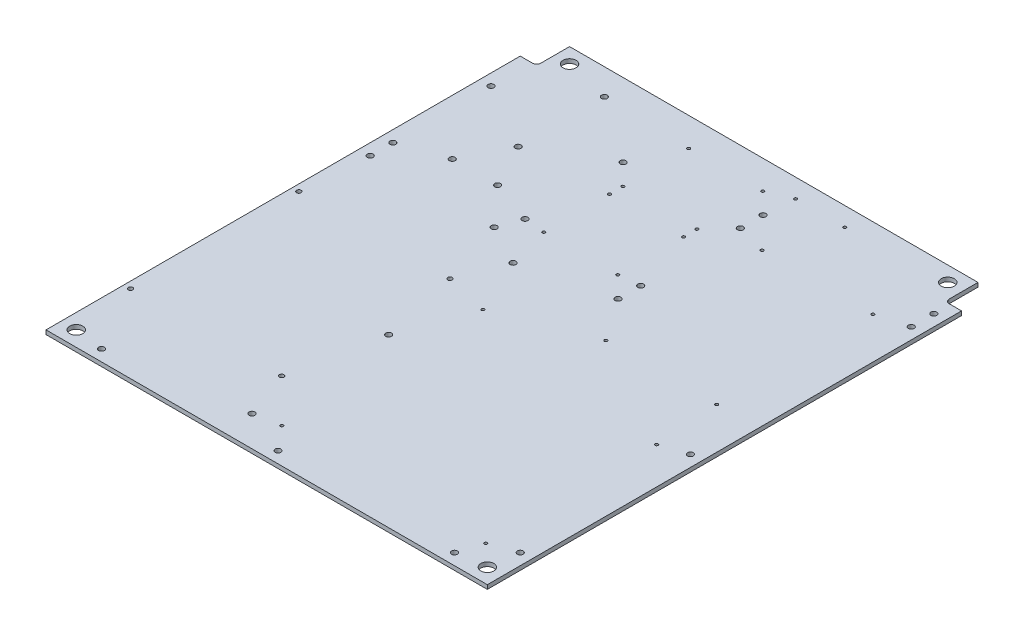
SolidWorks part; units mm, degrees
material "6061-T6 (SS)"
ref_plane "Front" through (0, 0, 0) normal (0, 0, 1) x (1, 0, 0)
ref_plane "Top" through (0, 0, 0) normal (0, 1, 0) x (1, 0, 0)
ref_plane "Right" through (0, 0, 0) normal (1, 0, 0) x (0, 0, -1)
sketch "Sketch1" plane through (0, 0, 0) normal (0, 1, 0) x (1, 0, 0)
  line L1 (170.434, -195.834) -> (-170.434, -195.834)
  line L2 (170.434, -195.834) -> (170.434, 195.834)
  line L3 (170.434, 195.834) -> (-170.434, 195.834)
  line L4 (-170.434, -195.834) -> (-170.434, 195.834)
  line L5 (170.434, -195.834) -> (-170.434, 195.834) construction
  line L6 (170.434, 195.834) -> (-170.434, -195.834) construction
  point P0 (0, 0)
  dimension "D1" = 340.868
  dimension "D2" = 391.668
extrude "Boss-Extrude1" add sketch "Sketch1" along normal blind 3.175
sketch "Sketch2" plane through (0, 3.175, 0) normal (0, 1, 0) x (1, 0, 0)
  line L0 (170.434, 195.834) -> (-170.434, 195.834) construction
  line L1 (-170.434, 195.834) -> (-157.734, 195.834)
  line L2 (-170.434, 195.834) -> (-170.434, 170.434)
  line L3 (-170.434, 170.434) -> (-160.909, 170.434)
  line L4 (-157.734, 195.834) -> (-157.734, 173.609)
  line L5 (170.434, 195.834) -> (157.734, 195.834)
  line L6 (170.434, 195.834) -> (170.434, 170.434)
  line L7 (170.434, 170.434) -> (160.909, 170.434)
  line L8 (157.734, 195.834) -> (157.734, 173.609)
  arc A0 (-157.734, 173.609) -> (-160.909, 170.434) centre (-160.909, 173.609) cw
  arc A1 (157.734, 173.609) -> (160.909, 170.434) centre (160.909, 173.609) ccw
  dimension "D1" = 3.175
  dimension "D2" = 25.4
  dimension "D3" = 12.7
extrude "Cut-Extrude1" cut sketch "Sketch2" against normal blind 10
hole_wizard "3/8 Clearance Hole1" positions "Sketch3" profile "Sketch4" hole size "3/8" standard "ANSI Inch" end condition through all
sketch "Sketch3" plane through (0, 3.175, 0) normal (0, 1, 0) x (1, 0, 0)
  line L0 (158.75, -184.15) -> (0, -184.15) construction
  line L1 (0, -184.15) -> (-158.75, -184.15) construction
  line L2 (-158.75, -184.15) -> (-158.75, -12.7) construction
  line L3 (-158.75, -12.7) -> (-158.75, 158.75) construction
  line L4 (-158.75, 158.75) -> (158.75, 158.75) construction
  line L5 (158.75, 158.75) -> (158.75, -12.7) construction
  line L6 (158.75, -12.7) -> (158.75, -184.15) construction
  line L8 (146.05, 184.15) -> (0, 184.15) construction
  line L9 (0, 184.15) -> (-146.05, 184.15) construction
  line L10 (-146.05, 184.15) -> (-157.734, 195.834) construction
  line L12 (157.734, 195.834) -> (146.05, 184.15) construction
  line L14 (-158.75, 158.75) -> (-170.434, 170.434) construction
  line L16 (-158.75, -184.15) -> (-170.434, -195.834) construction
  line L18 (158.75, 158.75) -> (170.434, 170.434) construction
  line L20 (158.75, -184.15) -> (170.434, -195.834) construction
  line L21 (158.75, -184.15) -> (158.75, -195.834) construction
  line L22 (-170.434, -195.834) -> (170.434, -195.834) construction
  line L24 (158.75, -184.15) -> (170.434, -184.15) construction
  line L25 (170.434, -195.834) -> (170.434, 170.434) construction
  point P0 (158.75, -184.15)
  point P2 (-158.75, -184.15)
  point P94 (-146.05, 184.15)
  point P96 (146.05, 184.15)
  dimension "D1" = 11.684
sketch "Sketch4" plane through (158.75, 3.175, 184.15) normal (1, 0, 0) x (0, 0, 1)
  line L0 (0, 0) -> (0, 3.175)
  line L1 (0, 3.175) -> (5.0419, 3.175)
  line L2 (5.0419, 3.175) -> (5.0419, 0)
  line L5 (5.0419, 0) -> (0, 0)
  line L11 (0, -6.35) -> (0, 107.95) construction
  dimension "Thru Hole Dia." = 10.0838
  dimension "Thru Hole Depth" = 3.175
hole_wizard "#4-40 Tapped Hole1" positions "Sketch5" profile "Sketch6" tap size "#4-40" standard "ANSI Inch" end condition through all
sketch "Sketch5" plane through (0, 3.175, 0) normal (0, 1, 0) x (1, 0, 0)
  point P0 (-15.34, -13.51)
  point P3 (142.14, -36.73)
  point P6 (142.14, -168.81)
  point P9 (-15.34, -168.81)
  point P12 (-43.575, 61.759)
  point P15 (13.575, 61.759)
  point P18 (13.575, 112.559)
  point P21 (-43.575, 112.559)
  point P24 (-43.575, 122.909)
  point P27 (-43.575, 173.709)
  point P30 (13.575, 173.709)
  point P33 (13.575, 122.909)
cosmetic thread "Hole Thread1" parameters "D2"=2.8448
cosmetic thread "Hole Thread2" parameters "D2"=2.8448
cosmetic thread "Hole Thread3" parameters "D2"=2.8448
cosmetic thread "Hole Thread4" parameters "D2"=2.8448
cosmetic thread "Hole Thread9" parameters "D2"=2.8448
cosmetic thread "Hole Thread10" parameters "D2"=2.8448
cosmetic thread "Hole Thread11" parameters "D2"=2.8448
cosmetic thread "Hole Thread12" parameters "D2"=2.8448
cosmetic thread "Hole Thread13" parameters "D2"=2.8448
cosmetic thread "Hole Thread14" parameters "D2"=2.8448
cosmetic thread "Hole Thread15" parameters "D2"=2.8448
cosmetic thread "Hole Thread16" parameters "D2"=2.8448
sketch "Sketch6" plane through (-15.34, 3.175, 13.51) normal (1, 0, 0) x (0, 0, 1)
  line L0 (0, 0) -> (0, 3.175)
  line L1 (0, 3.175) -> (1.1303, 3.175)
  line L2 (1.1303, 3.175) -> (1.1303, 0)
  line L5 (1.1303, 0) -> (0, 0)
  line L11 (0, -6.35) -> (0, 107.95) construction
  dimension "Thru Tap Drill Dia." = 2.2606
  dimension "Thru Tap Drill Depth" = 3.175
hole_wizard "#8-32 Tapped Hole1" positions "Sketch7" profile "Sketch8" tap size "#8-32" standard "ANSI Inch" end condition through all
sketch "Sketch7" plane through (0, 3.175, 0) normal (0, 1, 0) x (1, 0, 0)
  arc A0 (-165.334, -7.875) -> (-165.334, -3.375) centre (-165.334, -5.625) ccw construction
  arc A1 (-165.334, -137.875) -> (-165.334, -133.375) centre (-165.334, -135.625) ccw construction
  arc A2 (-48.634, -3.375) -> (-48.634, -7.875) centre (-48.634, -5.625) ccw construction
  arc A3 (-48.634, -133.375) -> (-48.634, -137.875) centre (-48.634, -135.625) ccw construction
  point P0 (-165.334, -5.625)
  point P2 (-165.334, -135.625)
  point P5 (-48.634, -135.625)
  point P9 (-48.634, -5.625)
cosmetic thread "Hole Thread5" parameters "D2"=4.1656
cosmetic thread "Hole Thread6" parameters "D2"=4.1656
cosmetic thread "Hole Thread7" parameters "D2"=4.1656
cosmetic thread "Hole Thread8" parameters "D2"=4.1656
sketch "Sketch8" plane through (-165.334, 3.175, 5.625) normal (1, 0, 0) x (0, 0, 1)
  line L0 (0, 0) -> (0, 3.175)
  line L1 (0, 3.175) -> (1.7272, 3.175)
  line L2 (1.7272, 3.175) -> (1.7272, 0)
  line L5 (1.7272, 0) -> (0, 0)
  line L11 (0, -6.35) -> (0, 107.95) construction
  dimension "Thru Tap Drill Dia." = 3.4544
  dimension "Thru Tap Drill Depth" = 3.175
hole_wizard "#4-40 Tapped Hole2" positions "Sketch9" profile "Sketch10" tap size "#4-40" standard "ANSI Inch" end condition through all
sketch "Sketch9" plane through (0, 3.175, 0) normal (0, 1, 0) x (1, 0, 0)
  circle A0 centre (52.859, 133.909) radius 1.6319 construction
  circle A1 centre (138.509, 133.909) radius 1.6319 construction
  circle A2 centre (138.509, 13.259) radius 1.6319 construction
  circle A3 centre (52.859, 13.259) radius 1.6319 construction
  point P0 (138.509, 13.259)
  point P2 (52.859, 13.259)
  point P4 (138.509, 133.909)
  point P6 (52.859, 133.909)
cosmetic thread "Hole Thread17" parameters "D2"=2.8448
cosmetic thread "Hole Thread18" parameters "D2"=2.8448
cosmetic thread "Hole Thread19" parameters "D2"=2.8448
cosmetic thread "Hole Thread20" parameters "D2"=2.8448
sketch "Sketch10" plane through (138.509, 3.175, -13.259) normal (1, 0, 0) x (0, 0, 1)
  line L0 (0, 0) -> (0, 3.175)
  line L1 (0, 3.175) -> (1.1303, 3.175)
  line L2 (1.1303, 3.175) -> (1.1303, 0)
  line L5 (1.1303, 0) -> (0, 0)
  line L11 (0, -6.35) -> (0, 107.95) construction
  dimension "Thru Tap Drill Dia." = 2.2606
  dimension "Thru Tap Drill Depth" = 3.175
hole_wizard "#4-40 Tapped Hole3" positions "Sketch11" profile "Sketch12" tap size "#4-40" standard "ANSI Inch" end condition through all
sketch "Sketch11" plane through (0, 3.175, 0) normal (0, 1, 0) x (1, 0, 0)
  point P0 (69.434, 181.209)
  point P3 (31.434, 181.209)
cosmetic thread "Hole Thread21" parameters "D2"=2.8448
cosmetic thread "Hole Thread22" parameters "D2"=2.8448
sketch "Sketch12" plane through (69.434, 3.175, -181.209) normal (1, 0, 0) x (0, 0, 1)
  line L0 (0, 0) -> (0, 3.175)
  line L1 (0, 3.175) -> (1.1303, 3.175)
  line L2 (1.1303, 3.175) -> (1.1303, 0)
  line L5 (1.1303, 0) -> (0, 0)
  line L11 (0, -6.35) -> (0, 107.95) construction
  dimension "Thru Tap Drill Dia." = 2.2606
  dimension "Thru Tap Drill Depth" = 3.175
hole_wizard "#8 Clearance Hole1" positions "Sketch13" profile "Sketch14" hole size "#8" standard "ANSI Inch" end condition through all
sketch "Sketch13" plane through (0, 3.175, 0) normal (0, 1, 0) x (1, 0, 0)
  line L0 (-92.8222, 75.3083) -> (-127.8222, 75.3083)
  line L2 (-170.434, 170.434) -> (-170.434, -195.834) construction
  line L3 (-170.434, 170.434) -> (-160.909, 170.434) construction
  line L4 (-161.684, 139.084) -> (-161.684, 45.834)
  line L6 (-170.434, 170.434) -> (-170.434, -195.834) construction
  line L7 (161.684, 157.834) -> (161.684, -161.684)
  line L9 (170.434, -195.834) -> (170.434, 170.434) construction
  line L10 (29.684, 157.834) -> (29.684, 45.834)
  line L12 (-161.684, 45.834) -> (29.684, 45.834)
  line L14 (-59.684, 139.084) -> (-59.684, 45.834)
  line L16 (-34.884, 45.834) -> (-34.884, -187.084)
  line L18 (-136.284, -187.084) -> (136.284, -187.084)
  line L20 (136.284, -187.084) -> (161.684, -187.084)
  line L21 (161.684, -187.084) -> (161.684, -161.684)
  line L22 (-170.434, -195.834) -> (170.434, -195.834) construction
  line L23 (157.734, 195.834) -> (-157.734, 195.834) construction
  line L24 (29.684, 157.834) -> (161.684, 157.834)
  line L26 (29.684, 140.334) -> (161.684, 140.334) construction
  line L28 (-161.684, 63.334) -> (29.684, 63.334) construction
  line L30 (-110.684, 175.684) -> (-110.684, 109.084)
  point P0 (-127.8222, 75.3083)
  point P2 (-92.8222, 75.3083)
  point P14 (-59.684, 139.084)
  point P16 (-59.684, 63.334)
  point P18 (-161.684, 45.834)
  point P20 (-161.684, 63.334)
  point P22 (-161.684, 139.084)
  point P24 (29.684, 45.834)
  point P26 (29.684, 63.334)
  point P28 (29.684, 140.334)
  point P30 (29.684, 157.834)
  point P32 (161.684, 157.834)
  point P34 (161.684, 140.334)
  point P36 (161.684, -161.684)
  point P38 (161.684, -30.2348)
  point P40 (136.284, -187.084)
  point P42 (0, -187.084)
  point P44 (-136.284, -187.084)
  point P46 (-34.884, -172.318)
  point P48 (-34.884, 29.3268)
  point P50 (-34.884, -66.7746)
  point P52 (-66, 45.834)
  point P124 (-110.684, 175.684)
  point P126 (-110.684, 109.084)
  dimension "D1" = 35
  dimension "D2" = 42.6118
  dimension "D3" = 95.1257
  dimension "D4" = 8.75
  dimension "D5" = 8.75
  dimension "D6" = 25.4
  dimension "D7" = 25.4
  dimension "D8" = 8.75
  dimension "D9" = 56.75
  dimension "D10" = 102
  dimension "D11" = 38
  dimension "D12" = 17.5
  dimension "D13" = 17.5
  dimension "D14" = 132
  dimension "D15" = 112
  dimension "D16" = 126.8
  dimension "D17" = 20.15
  dimension "D18" = 66.6
  dimension "D19" = 59.75
sketch "Sketch14" plane through (-127.8222, 3.175, -75.3083) normal (1, 0, 0) x (0, 0, 1)
  line L0 (0, 0) -> (0, 3.175)
  line L1 (0, 3.175) -> (2.2479, 3.175)
  line L2 (2.2479, 3.175) -> (2.2479, 0)
  line L5 (2.2479, 0) -> (0, 0)
  line L11 (0, -6.35) -> (0, 107.95) construction
  dimension "Thru Hole Dia." = 4.4958
  dimension "Thru Hole Depth" = 3.175
